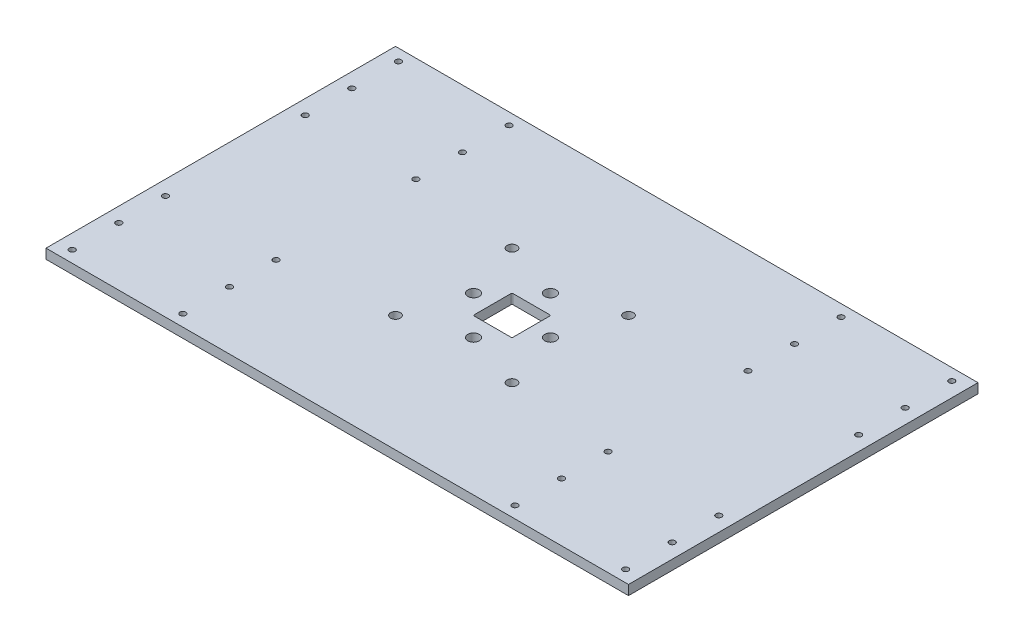
SolidWorks part; units mm, degrees
ref_plane "Front Plane" through (0, 0, 0) normal (0, 0, 1) x (1, 0, 0)
ref_plane "Top Plane" through (0, 0, 0) normal (0, 1, 0) x (1, 0, 0)
ref_plane "Right Plane" through (0, 0, 0) normal (1, 0, 0) x (0, 0, -1)
sketch "Sketch1" plane through (0, 0, 0) normal (0, 1, 0) x (1, 0, 0)
  line L0 (-142.5, 90) -> (-142.5, -90) construction
  line L1 (-150, -90) -> (150, -90)
  line L2 (-150, -90) -> (-150, 90)
  line L3 (-150, 90) -> (150, 90)
  line L4 (150, -90) -> (150, 90)
  line L5 (-150, -90) -> (150, 90) construction
  line L6 (-150, 90) -> (150, -90) construction
  line L7 (0, 0) -> (-30, -30) construction
  line L8 (0, 90) -> (0, -90) construction
  line L9 (-150, 0) -> (150, 0) construction
  line L10 (-9.5, -10) -> (9.5, -10)
  line L11 (-10, -9.5) -> (-10, 9.5)
  line L12 (-9.5, 10) -> (9.5, 10)
  line L13 (10, -9.5) -> (10, 9.5)
  line L14 (-10, -10) -> (10, 10) construction
  line L15 (-10, 10) -> (10, -10) construction
  circle A0 centre (-142.5, 84) radius 1.5
  circle A1 centre (-142.5, 60) radius 1.5
  circle A2 centre (-142.5, 36) radius 1.5
  circle A3 centre (-85.5, 84) radius 1.5
  circle A4 centre (-85.5, 60) radius 1.5
  circle A5 centre (-85.5, 36) radius 1.5
  circle A6 centre (85.5, 36) radius 1.5
  circle A7 centre (85.5, 60) radius 1.5
  circle A8 centre (85.5, 84) radius 1.5
  circle A9 centre (142.5, 36) radius 1.5
  circle A10 centre (142.5, 60) radius 1.5
  circle A11 centre (142.5, 84) radius 1.5
  circle A12 centre (142.5, -84) radius 1.5
  circle A13 centre (142.5, -60) radius 1.5
  circle A14 centre (142.5, -36) radius 1.5
  circle A15 centre (85.5, -84) radius 1.5
  circle A16 centre (85.5, -60) radius 1.5
  circle A17 centre (85.5, -36) radius 1.5
  circle A18 centre (-85.5, -36) radius 1.5
  circle A19 centre (-85.5, -60) radius 1.5
  circle A20 centre (-85.5, -84) radius 1.5
  circle A21 centre (-142.5, -36) radius 1.5
  circle A22 centre (-142.5, -60) radius 1.5
  circle A23 centre (-142.5, -84) radius 1.5
  arc A24 (9.5, 10) -> (10, 9.5) centre (9.5, 9.5) cw
  arc A25 (10, -9.5) -> (9.5, -10) centre (9.5, -9.5) cw
  arc A26 (-9.5, -10) -> (-10, -9.5) centre (-9.5, -9.5) cw
  arc A27 (-10, 9.5) -> (-9.5, 10) centre (-9.5, 9.5) cw
  circle A28 centre (0, 19.8) radius 2.95
  circle A29 centre (19.8, 0) radius 2.95
  circle A30 centre (0, -19.8) radius 2.95
  circle A31 centre (-19.8, 0) radius 2.95
  circle A33 centre (-30, -30) radius 2.5
  circle A34 centre (-30, 30) radius 2.5
  circle A35 centre (30, 30) radius 2.5
  circle A36 centre (30, -30) radius 2.5
  point P0 (0, 0)
  point P59 (0, 0)
  point P81 (37.1844, -47.0853)
  point P88 (0, 0)
  point P90 (0, 0)
  point P98 (0, 0)
  dimension "D5" = 3
  dimension "D9" = 0.5
  dimension "D10" = 9.8
  dimension "D11" = 5.9
  dimension "D14" = 57
  dimension "D15" = 45
  dimension "D17" = 60
  dimension "D18" = 5
  dimension "D1" = 300
  dimension "D2" = 180
  dimension "D3" = 7.5
  dimension "D4" = 3
  dimension "D6" = 6
  dimension "D8" = 20
  dimension "D13" = 24
  dimension "D7" = 2
  dimension "D12" = 4
  dimension "D16" = 4
extrude "Boss-Extrude1" add sketch "Sketch1" along normal blind 5
